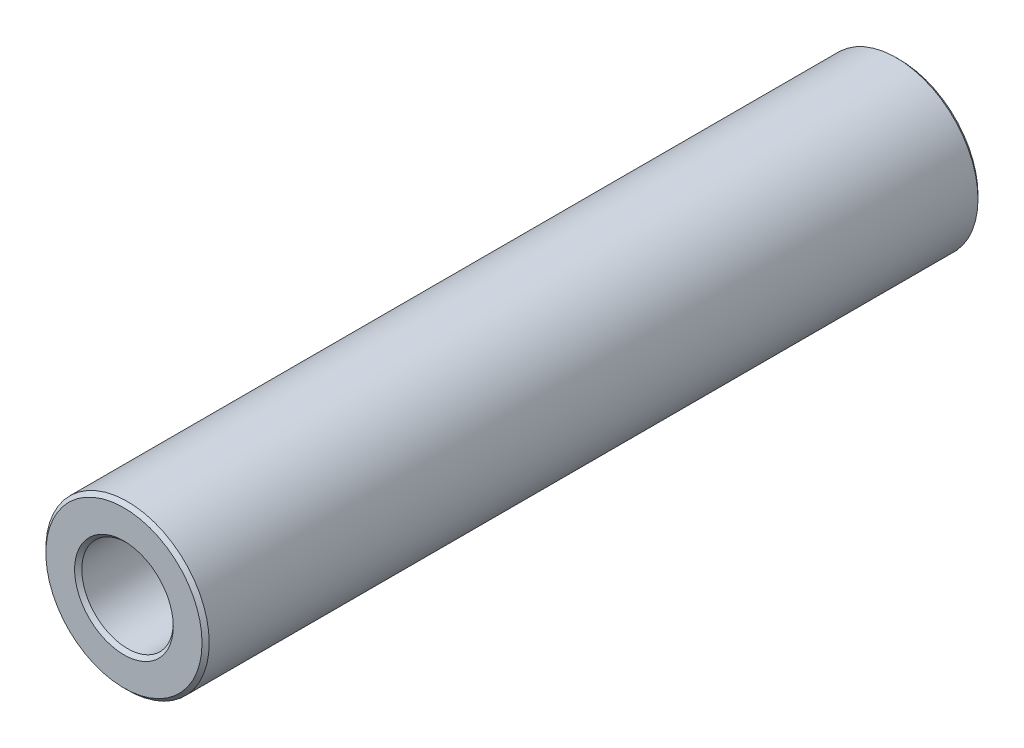
SolidWorks part; units mm, degrees
ref_plane "Front Plane" through (0, 0, 0) normal (0, 0, 1) x (1, 0, 0)
ref_plane "Top Plane" through (0, 0, 0) normal (0, 1, 0) x (1, 0, 0)
ref_plane "Right Plane" through (0, 0, 0) normal (1, 0, 0) x (0, 0, -1)
sketch "Sketch1" plane through (0, 0, 0) normal (0, 0, 1) x (1, 0, 0)
  circle A0 centre (0, 0) radius 3.175 construction
  circle A1 centre (0, 0) radius 1.778 construction
  point P4 (0, 3.175)
  dimension "ID" = 3.556
  dimension "OD" = 6.35
sketch "Sketch2" plane through (0, 0, 0) normal (1, 0, 0) x (0, 0, -1)
  line L0 (-15.0812, 3.175) -> (15.0812, 3.175) construction
  dimension "Length" = 30.1625
sketch "Sketch3" plane through (0, 0, 0) normal (0, 0, 1) x (1, 0, 0)
  circle A0 centre (0, 0) radius 1.778 construction
  circle A1 centre (0, 0) radius 3.175 construction
  circle A2 centre (0, 0) radius 1.778
  circle A3 centre (0, 0) radius 3.175
extrude "Boss-Extrude1" add sketch "Sketch3" against normal up to vertex (15.0813 mm away) and the other way up to vertex (15.0813 mm away) up to point (0, 3.175, -15.0812) other way up to point (0, 3.175, 15.0812)
chamfer "Chamfer1" distance 0.1397 angle 45 4 edges at (3.175, 0, 15.0812) (3.175, 0, -15.0812) (1.778, 0, 15.0812) (1.778, 0, -15.0812)
equation "\"D1@Chamfer1\"=(\"OD@Sketch1\"-\"ID@Sketch1\")*0.05"
